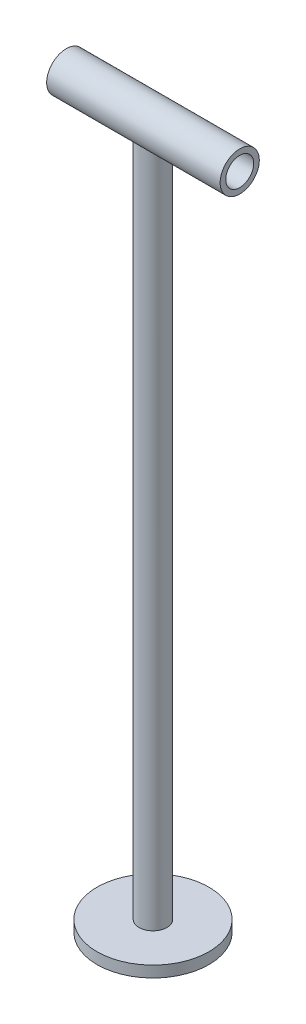
SolidWorks part; units mm, degrees
material "Plain Carbon Steel"
ref_plane "Front Plane" through (0, 0, 0) normal (0, 0, 1) x (1, 0, 0)
ref_plane "Top Plane" through (0, 0, 0) normal (0, 1, 0) x (1, 0, 0)
ref_plane "Right Plane" through (0, 0, 0) normal (1, 0, 0) x (0, 0, -1)
sketch "klip_Sketch1" plane through (0, 0, 0) normal (0, 1, 0) x (1, 0, 0)
  circle A0 centre (0, 0) radius 100
  dimension "D1" = 200
extrude "klip_Boss-Extrude1" add sketch "klip_Sketch1" against normal blind 20 contours A0
sketch "klip_Sketch3" plane through (0, 0, 0) normal (1, 0, 0) x (0, 0, -1)
  circle A0 centre (0, 1235) radius 35
  circle A1 centre (0, 1235) radius 25
  dimension "D3" = 50
  dimension "D1" = 70
  dimension "D2" = 1235
extrude "klip_Boss-Extrude3" add sketch "klip_Sketch3" along normal blind 155 and the other way blind 155 separate body
sketch "klip_Sketch2" plane through (0, 0, 0) normal (0, 1, 0) x (1, 0, 0)
  circle A0 centre (0, 0) radius 25
  dimension "D1" = 50
extrude "klip_Boss-Extrude2" add sketch "klip_Sketch2" along normal up to surface (1210.5051 mm away) contours A0 up to face at (-155, 1235, -35)
equation "\"sirina_klipa\"= 200"
equation "\"debljina_klipa\"= 20"
equation "\"sirina_klipnjace\"= \"sirina_klipa\" / 4"
equation "\"duljina_klipnjace\"= 1200"
equation "\"r2_v\"= 70"
equation "\"r2_u\"= 50"
equation "\"r1_v\"= 70"
equation "\"r1_u\"= 50"
equation "\"l2\"= 310"
equation "\"l1\"= 310"
equation "\"sirina_cilindra\"= \"sirina_klipa\" + \"debljina_stijenke\" * 2"
equation "\"duljina_komore\"= 30"
equation "\"debljina_stijenke\"= 10"
equation "\"D3@cilindar_Sketch1\"= \"duljina_komore\""
equation "\"D4@cilindar_Sketch1\"=\"sirina_klipa\"/2"
equation "\"D1@cilindar_Sketch1\"=\"sirina_cilindra\"/2"
equation "\"D2@cilindar_Sketch1\"= \"duljina_cilindra\""
equation "\"D1@cilindar_Shell1\"=\"debljina_stijenke\""
equation "\"duljina_cilindra\"= \"duljina_klipnjace\" + \"debljina_klipa\" + \"debljina_stijenke\" - \"duljina_komore\""
equation "\"D1@cilindar_Sketch2\"=\"duljina_cilindra\"/2 + \"duljina_komore\" + \"r1_v\"/2 + 1"
equation "\"D2@cilindar_Sketch2\"=\"r1_v\""
equation "\"D3@cilindar_Sketch2\"=\"r1_u\""
equation "\"D1@cilindar_Sketch7\" = \"sirina_klipnjace\""
equation "\"D2@cilindar_Boss-Extrude1\"=\"l1\"/2"
equation "\"D1@cilindar_Boss-Extrude1\"=\"l1\"/2"
equation "\"D1@klip_Boss-Extrude1\"=\"debljina_klipa\""
equation "\"D1@klip_Sketch1\"=\"sirina_klipa\""
equation "\"D2@klip_Sketch3\"= \"duljina_klipnjace\" + \"r2_v\" / 2"
equation "\"D3@klip_Sketch3\" = \"r2_u\""
equation "\"D1@klip_Sketch3\"=\"r2_v\""
equation "\"D1@klip_Boss-Extrude3\"=\"l1\"/2"
equation "\"D2@klip_Boss-Extrude3\"=\"l1\"/2"
